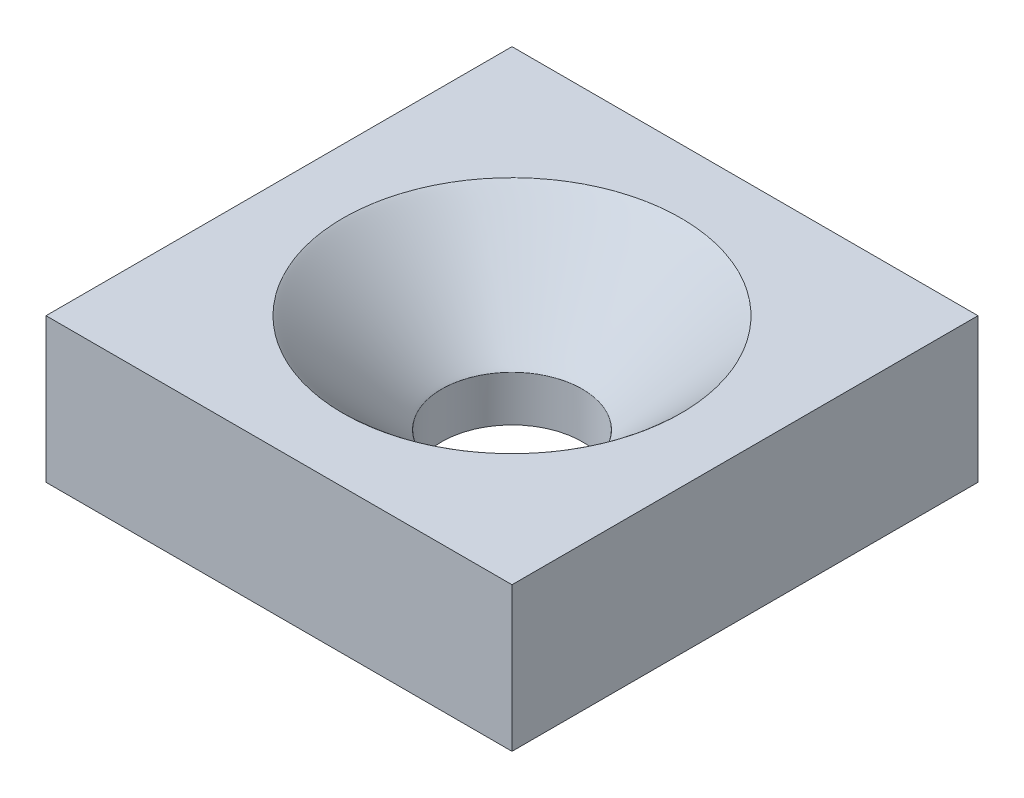
SolidWorks part; units mm, degrees
ref_plane "Front Plane" through (0, 0, 0) normal (0, 0, 1) x (1, 0, 0)
ref_plane "Top Plane" through (0, 0, 0) normal (0, 1, 0) x (1, 0, 0)
ref_plane "Right Plane" through (0, 0, 0) normal (1, 0, 0) x (0, 0, -1)
sketch "Sketch1" plane through (0, 0, 0) normal (0, 1, 0) x (1, 0, 0)
  line L1 (-7.789, 7.789) -> (7.789, 7.789)
  line L2 (-7.789, 7.789) -> (-7.789, -7.789)
  line L3 (-7.789, -7.789) -> (7.789, -7.789)
  line L4 (7.789, 7.789) -> (7.789, -7.789)
  line L5 (-7.789, 7.789) -> (7.789, -7.789) construction
  line L6 (-7.789, -7.789) -> (7.789, 7.789) construction
extrude "Boss-Extrude2" add sketch "Sketch1" along normal blind 10
sketch "Sketch2" plane through (0, 10, 0) normal (0, 1, 0) x (1, 0, 0)
  circle A0 centre (0, 0) radius 2.35
  dimension "D1" = 4.7
extrude "Cut-Extrude1" cut sketch "Sketch2" against normal through all both and the other way through all
fillet "Fillet3" radius 3.3 1 edges at (0, 10, 2.35) conic radius 140
sketch "Sketch8" plane through (0, 0, 0) normal (1, 0, 0) x (0, 0, -1)
  line L0 (-2.35, 6.7) -> (-2.35, 0) construction
  line L1 (-2.35, 6.7) -> (-4.9676, 9.3607) construction
  line L2 (-4.9676, 9.3607) -> (-2.35, 9.3607) construction
  spline S0 degree 2 poles (-5.65, 10) (-2.35, 10) (-2.35, 6.7) knots 0 0 0 1 1 1 weights 1 0.016668 1 construction
sketch "Sketch9" plane through (-7.789, 0, 0) normal (-1, 0, 0) x (0, 0, 1)
  line L1 (-8.8813, 5.1759) -> (8.4748, 5.1759)
  line L2 (-8.8813, 5.1759) -> (-8.8813, -5.7717)
  line L3 (-8.8813, -5.7717) -> (8.4748, -5.7717)
  line L4 (8.4748, 5.1759) -> (8.4748, -5.7717)
extrude "Cut-Extrude2" cut sketch "Sketch9" against normal through all both and the other way through all
